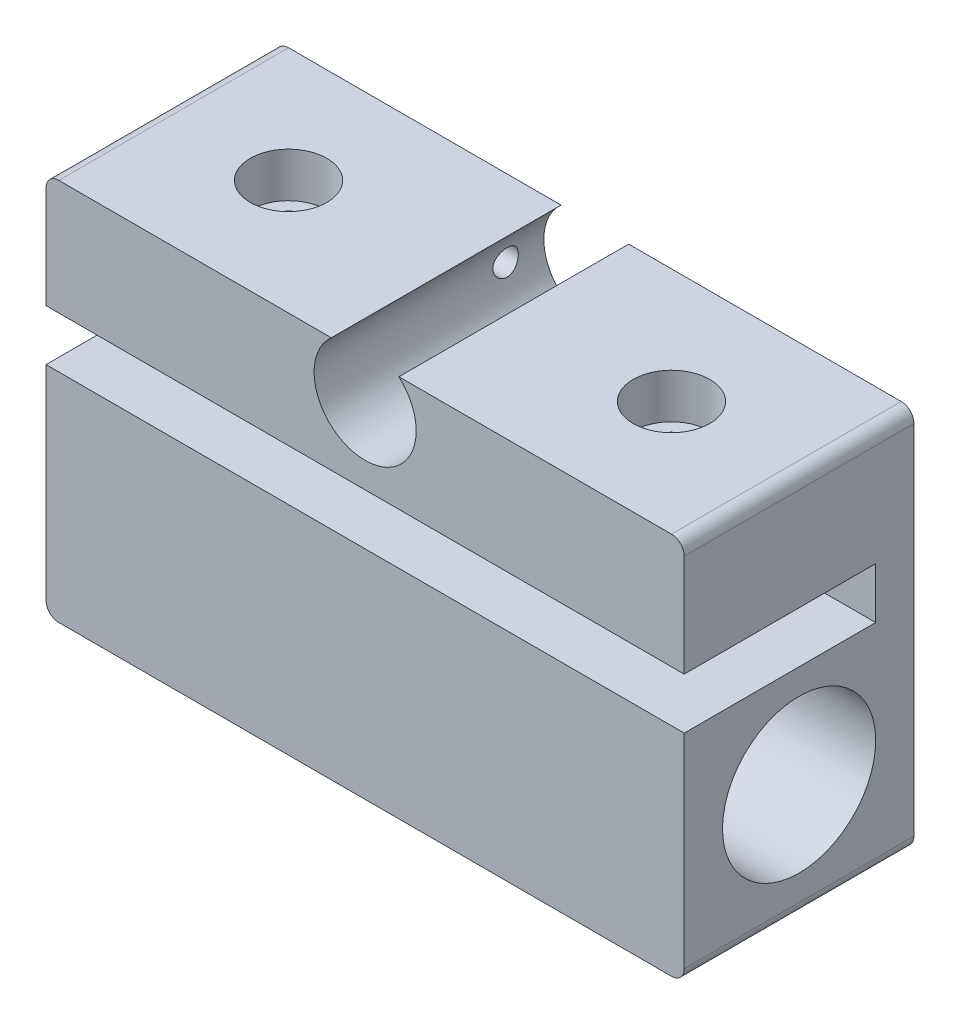
SolidWorks part; units mm, degrees
ref_plane "Front Plane" through (0, 0, 0) normal (0, 0, 1) x (1, 0, 0)
ref_plane "Top Plane" through (0, 0, 0) normal (0, 1, 0) x (1, 0, 0)
ref_plane "Right Plane" through (0, 0, 0) normal (1, 0, 0) x (0, 0, -1)
sketch "Sketch1" plane through (0, 0, 0) normal (0, 0, 1) x (1, 0, 0)
  line L0 (-25, 15) -> (25, 15)
  line L2 (-25, 15) -> (-25, -15)
  line L3 (-25, -15) -> (25, -15)
  line L4 (25, 15) -> (25, -15)
  line L5 (-25, 15) -> (25, -15) construction
  line L6 (-25, -15) -> (25, 15) construction
  point P0 (0, 0)
  point P4 (0, 0)
  point P8 (0, 0)
  dimension "D1" = 50
  dimension "D2" = 30
extrude "Boss-Extrude1" add sketch "Sketch1" along normal mid plane 18
sketch "Sketch2" plane through (-25, 0, 0) normal (-1, 0, 0) x (0, 0, 1)
  line L0 (0, 1.8022) -> (0, -4.9662) construction
  circle A0 centre (0, -6) radius 6
  dimension "D1" = 12
  dimension "D2" = 6
extrude "Cut-Extrude1" cut sketch "Sketch2" against normal through all
sketch "Sketch3" plane through (0, 0, 9) normal (0, 0, 1) x (1, 0, 0)
  line L0 (0, 0) -> (0, 7.3584) construction
  line L4 (25, -15) -> (25, 15)
  line L14 (25, -15) -> (25, 15)
  line L18 (25, 15) -> (-25, 15)
  line L23 (-25, 15) -> (-25, -15)
  line L24 (-25, 15) -> (-25, -15)
  line L25 (-25, -15) -> (25, -15)
  line L26 (-25, -15) -> (25, -15)
  line L27 (25, 15) -> (-25, 15)
  circle A0 centre (0, 12) radius 4
  dimension "D2" = 8
  dimension "D3" = 12
  dimension "D1" = 0
extrude "Cut-Extrude2" cut sketch "Sketch3" against normal through all contours A0 | A0 region at (0, 11.7353, 9)
sketch "Sketch4" plane through (0, 0, 9) normal (0, 0, 1) x (1, 0, 0)
  line L0 (-25, 15) -> (-25, -15) construction
  line L1 (-25, 6) -> (25, 6)
  line L2 (-25, 6) -> (-25, 2)
  line L4 (25, 6) -> (25, 2)
  line L5 (25, -15) -> (25, 15) construction
  line L12 (-25, 2) -> (25, 2)
  dimension "D1" = 4
  dimension "D4" = 6
extrude "Cut-Extrude3" cut sketch "Sketch4" against normal blind 15
sketch "Sketch5" plane through (-25, 0, 0) normal (-1, 0, 0) x (0, 0, 1)
  line L0 (9, 15) -> (9, 6) construction
  line L2 (9, 15) -> (-9, 15) construction
  circle A0 centre (-6, 12) radius 1
  dimension "D1" = 2
  dimension "D2" = 15
  dimension "D3" = 3
extrude "Cut-Extrude4" cut sketch "Sketch5" against normal blind 25
sketch "Sketch6" plane through (-25, 0, 0) normal (-1, 0, 0) x (0, 0, 1)
  circle A0 centre (-6, 12) radius 1.5
  dimension "D1" = 3
extrude "Cut-Extrude5" cut sketch "Sketch6" against normal blind 5
sketch "Sketch7" plane through (0, 15, 0) normal (0, 1, 0) x (1, 0, 0)
  line L0 (-5.9792, 0) -> (7.2933, 0) construction
  line L1 (0, 5.7492) -> (0, -5.4207) construction
  circle A0 centre (-15, 0) radius 2
  circle A1 centre (15, 0) radius 2
  dimension "D1" = 4
  dimension "D2" = 15
extrude "Cut-Extrude6" cut sketch "Sketch7" against normal up to next
hole_wizard "CBORE for M5 Hex Head Bolt1" positions "3DSketch1" profile "Sketch9" counterbore size "M5" standard "ISO"
sketch3d "3DSketch1"
  line L0 (-15, 6, 0) -> (-15, 15, 0) construction
  line L1 (15, 6, 0) -> (15, 15, 0) construction
  point P0 (-15, 15, 0)
  point P4 (15, 15, 0)
sketch "Sketch9" plane through (-15, 15, 0) normal (1, 0, 0) x (0, 0, 1)
  line L0 (0, 0) -> (0, 11.2017)
  line L1 (0, 11.2017) -> (2, 10)
  line L2 (2, 10) -> (2, 3.5)
  line L3 (2, 3.5) -> (3, 3.5)
  line L4 (3, 3.5) -> (3, 0)
  line L5 (3, 0) -> (0, 0)
  line L10 (0, 11.2017) -> (-2, 10) construction
  line L11 (0, -6.35) -> (0, 107.95) construction
  dimension "Hole Dia." = 4
  dimension "Hole Depth" = 10
  dimension "C'Bore Dia." = 6
  dimension "C'Bore Depth" = 3.5
  dimension "Drill Angle" = 118
fillet "Fillet1" radius 1 4 edges at (-25, -15, 0) (25, -15, 0) (25, 15, 0) (-25, 15, 0)
